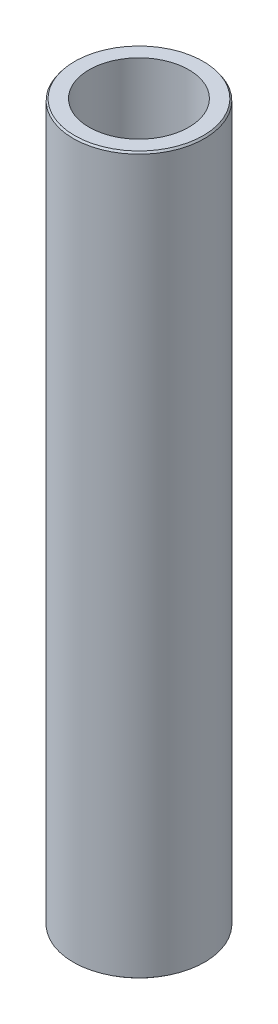
SolidWorks part; units mm, degrees
ref_plane "Front Plane" through (0, 0, 0) normal (0, 0, 1) x (1, 0, 0)
ref_plane "Top Plane" through (0, 0, 0) normal (0, 1, 0) x (1, 0, 0)
ref_plane "Right Plane" through (0, 0, 0) normal (1, 0, 0) x (0, 0, -1)
sketch "Sketch1" plane through (0, 0, 0) normal (0, 1, 0) x (1, 0, 0)
  circle A0 centre (0, 0) radius 55
  dimension "SHAFT_OD" = 110
extrude "Boss-Extrude1" add sketch "Sketch1" along normal blind 600
sketch "Sketch2" plane through (0, 0, 0) normal (0, 1, 0) x (1, 0, 0)
  circle A0 centre (0, 0) radius 41.7442
  dimension "BORE_D" = 83.4884
extrude "Cut-Extrude1" cut sketch "Sketch2" along normal through all
chamfer "Chamfer1" distance 1.5283 angle 37.136 2 edges at (0, 600, 55) (0, 0, 55) first distance on face at (0, 600, 55) first distance on face at (0, 0, 41.7442)
